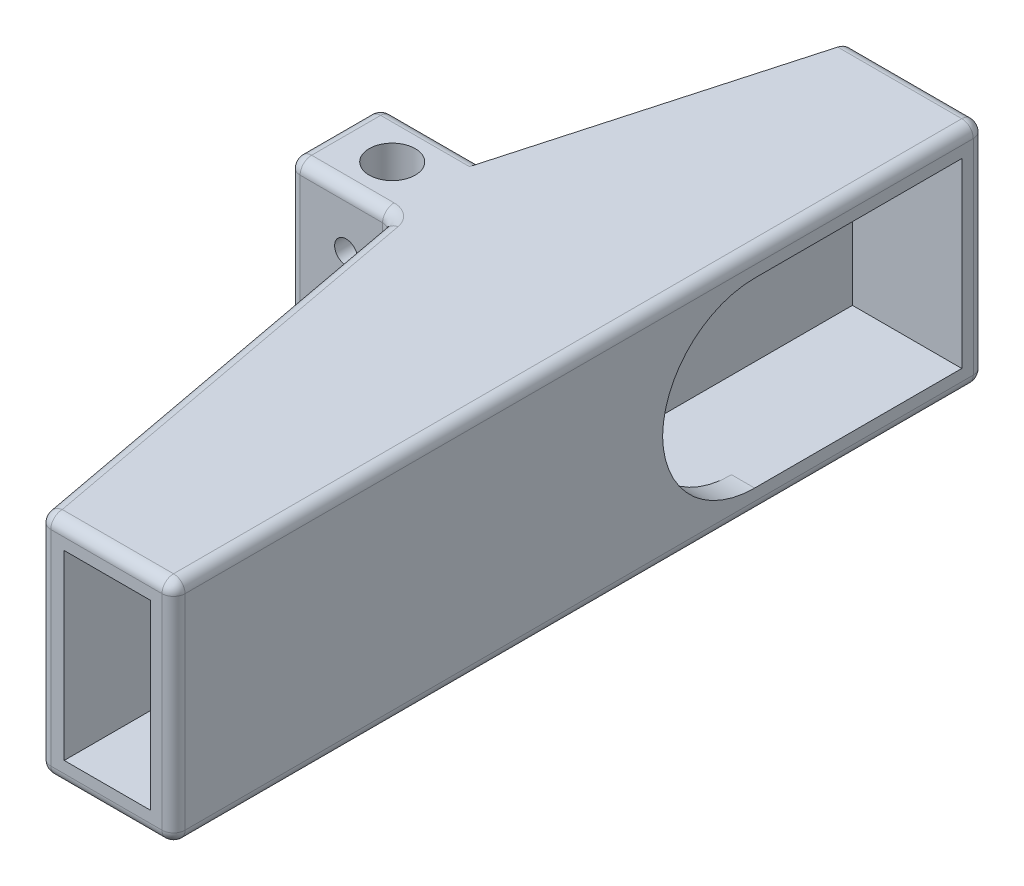
SolidWorks part; units mm, degrees
ref_plane "Alzado" through (0, 0, 0) normal (1, 0, 0) x (0, 1, 0)
ref_plane "Planta" through (0, 0, 0) normal (0, 0, 1) x (0, 1, 0)
ref_plane "Vista lateral" through (0, 0, 0) normal (0, 1, 0) x (-1, 0, 0)
sketch "Croquis1" plane through (0, 0, 0) normal (0, 0, 1) x (0, 1, 0)
  line L1 (-9.9, -5.75) -> (9.9, -5.75)
  line L2 (-9.9, -5.75) -> (-9.9, 5.75)
  line L3 (-9.9, 5.75) -> (9.9, 5.75)
  line L4 (9.9, -5.75) -> (9.9, 5.75)
  line L5 (-9.9, -5.75) -> (9.9, 5.75) construction
  line L6 (-9.9, 5.75) -> (9.9, -5.75) construction
  point P0 (0, 0)
  dimension "D1" = 19.8
  dimension "D2" = 11.5
extrude "Saliente-Extruir1" add sketch "Croquis1" along normal blind 70.5 contours L2 L1 L4 L3
shell "Vaciado1" thickness 2 removed face at (0, 0, 70.5)
sketch "Croquis4" plane through (5.75, 0, 0) normal (1, 0, 0) x (0, 1, 0)
sketch "Croquis5" plane through (5.75, 0, 0) normal (1, 0, 0) x (0, 1, 0)
  line L0 (-7.9, 70.5) -> (-7.9, 68.5)
  line L1 (-7.9, 70.5) -> (7.9, 70.5)
  line L2 (-7.9, 68.5) -> (7.9, 68.5)
  line L3 (7.9, 70.5) -> (7.9, 68.5)
  line L5 (-9.9, 70.5) -> (9.9, 70.5) construction
  dimension "D1" = 15.8
  dimension "D2" = 2
extrude "Saliente-Extruir2" add sketch "Croquis5" against normal blind 2 contours L0 L1 L3 L2
sketch "Croquis6" plane through (-5.75, 0, 0) normal (-1, 0, 0) x (0, -1, 0)
  line L0 (-9.9, 25) -> (9.9, 25)
  line L1 (-9.9, 25) -> (-9.9, 33)
  line L2 (9.9, 25) -> (9.9, 33)
  line L3 (-9.9, 33) -> (9.9, 33)
  line L4 (9.9, 0) -> (-9.9, 0) construction
  line L5 (-9.9, 70.5) -> (-9.9, 0) construction
  line L6 (9.9, 70.5) -> (9.9, 0) construction
  dimension "D1" = 8
  dimension "D2" = 25
extrude "Saliente-Extruir4" add sketch "Croquis6" along normal blind 16
sketch "Croquis9" plane through (0, -9.9, 0) normal (0, -1, 0) x (1, 0, 0)
  line L0 (-5.75, 70.5) -> (-12.75, 33)
  line L1 (-21.75, 33) -> (-5.75, 33) construction
  line L2 (-12.75, 33) -> (-5.75, 33)
  line L3 (-5.75, 33) -> (-5.75, 70.5)
  line L4 (-5.75, 0) -> (-12.75, 25)
  line L5 (-21.75, 25) -> (-5.75, 25) construction
  line L6 (-12.75, 25) -> (-5.75, 25)
  line L7 (-5.75, 25) -> (-5.75, 0) construction
  line L8 (-5.75, 25) -> (-5.75, 0)
  dimension "D1" = 7
  dimension "D2" = 7
extrude "Saliente-Extruir5" add sketch "Croquis9" against normal blind 19.8
sketch "Croquis10" plane through (0, -9.9, 0) normal (0, -1, 0) x (1, 0, 0)
  line L0 (-21.75, 25) -> (-21.75, 33) construction
  circle A0 centre (-16.7453, 29) radius 2
  point P4 (-21.75, 29)
  dimension "D1" = 4
  dimension "D2" = 5.0047
extrude "Cortar-Extruir4" cut sketch "Croquis10" against normal blind 19.8
sketch "Croquis8" plane through (-4, 0, 33) normal (0, 0, 1) x (1, 0, 0)
  line L0 (-17.75, -9.9) -> (-8.75, -9.9) construction
  line L1 (-17.75, -9.9) -> (-17.75, 9.9) construction
  circle A0 centre (-12.75, 5.1) radius 1
  circle A1 centre (-12.75, -4.9) radius 1
  dimension "D4" = 2
  dimension "D5" = 2
  dimension "D1" = 10
  dimension "D2" = 5
  dimension "D3" = 5
extrude "Cortar-Extruir3" cut sketch "Croquis8" against normal through all both and the other way through all contours A0 | A1 | A0 region at (-16.75, 5.1, 33)
sketch "Croquis11" plane through (5.75, 0, 0) normal (1, 0, 0) x (0, 1, 0)
  line L2 (-7.9, 2) -> (7.9, 2)
  line L6 (7.9, 2) -> (7.9, 28)
  line L7 (-7.9, 2) -> (-7.9, 28)
  line L8 (-7.9, 28) -> (7.9, 28)
extrude "Cortar-Extruir5" cut sketch "Croquis11" against normal blind 2
fillet "Redondeo2" radius 8 2 edges at (4.75, -7.9, 28) (4.75, 7.9, 28)
fillet "Redondeo4" radius 1 1 edges at (-12.75, 0, 33)
fillet "Redondeo5" radius 1 2 edges at (-5.75, 0, 70.5) (5.75, 0, 70.5)
fillet "Redondeo6" radius 1 14 edges at (5.75, 9.9, 34.75) (5.4571, 9.9, 70.2071) (-17.6653, 9.9, 33) (-12.9417, 9.9, 33.2307) (-9.25, 9.9, 51.75) (-5.5583, 9.9, 70.2693) (5.75, -9.9, 34.75) (5.4571, -9.9, 70.2071) (-17.6653, -9.9, 33) (-12.9417, -9.9, 33.2307) (-9.25, -9.9, 51.75) (-5.5583, -9.9, 70.2693) (-0.0847, 9.9, 70.5) (-0.0847, -9.9, 70.5)
fillet "Redondeo7" radius 1 6 edges at (-21.75, 0, 25) (5.4571, 9.6071, 0) (5.4571, -9.6071, 0) (5.75, 0, 0) (-0.5, -9.9, 0) (-0.5, 9.9, 0)
fillet "Redondeo8" radius 1 9 edges at (-21.75, 9.9, 29) (-21.75, 9.6071, 32.7071) (-21.75, -9.9, 29) (-21.75, -9.6071, 32.7071) (-21.75, 0, 33) (-16.75, -9.9, 25) (-21.4571, -9.9, 25.2929) (-16.75, 9.9, 25) (-21.4571, 9.9, 25.2929)
equation "\"15.8mm.\"=19.8"
